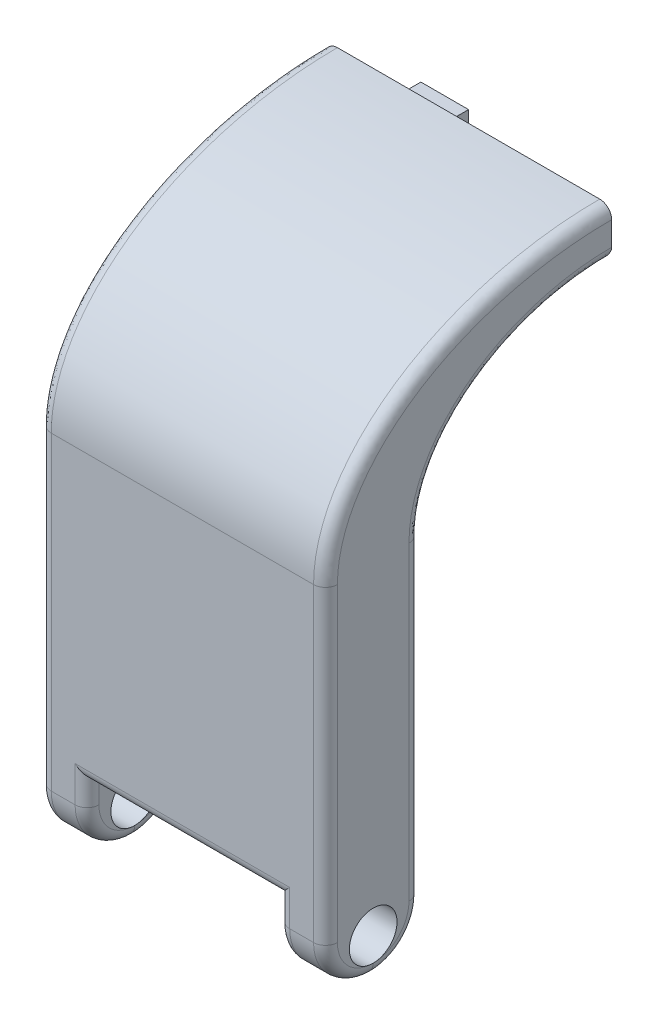
SolidWorks part; units mm, degrees
ref_plane "Front Plane" through (0, 0, 0) normal (0, 0, 1) x (1, 0, 0)
ref_plane "Top Plane" through (0, 0, 0) normal (0, 1, 0) x (1, 0, 0)
ref_plane "Right Plane" through (0, 0, 0) normal (1, 0, 0) x (0, 0, -1)
sketch "Sketch1" plane through (0, 0, 0) normal (0, 1, 0) x (1, 0, 0)
  line L1 (0, 0) -> (60, 0)
  line L2 (0, 0) -> (0, -20)
  line L3 (0, -20) -> (60, -20)
  line L4 (60, 0) -> (60, -20)
  dimension "D1" = 20
  dimension "D2" = 60
extrude "Boss-Extrude1" add sketch "Sketch1" against normal blind 30
sketch "Sketch2" plane through (0, -30, 0) normal (0, -1, 0) x (1, 0, 0)
  line L0 (60, 0) -> (0, 0) construction
  line L1 (10, 0) -> (50, 0)
  line L2 (10, 0) -> (10, 20)
  line L3 (10, 20) -> (50, 20)
  line L4 (50, 0) -> (50, 20)
  line L5 (0, 20) -> (60, 20) construction
  line L6 (0, 0) -> (0, 20) construction
  dimension "D1" = 40
  dimension "D2" = 10
extrude "Cut-Extrude1" cut sketch "Sketch2" against normal blind 15
sketch "Sketch3" plane through (10, 0, 0) normal (1, 0, 0) x (0, 0, -1)
  circle A0 centre (-10, -22.5) radius 5
  dimension "D1" = 10
extrude "Cut-Extrude2" cut sketch "Sketch3" against normal through all and the other way through all
sketch "Sketch5" plane through (0, 0, 0) normal (0, 1, 0) x (1, 0, 0)
  line L1 (0, 0) -> (60, 0)
  line L2 (0, 0) -> (0, -20)
  line L3 (0, -20) -> (60, -20)
  line L4 (60, 0) -> (60, -20)
extrude "Boss-Extrude2" add sketch "Sketch5" along normal blind 45
sketch "Sketch6" plane through (0, 0, 0) normal (1, 0, 0) x (0, 0, -1)
  line L0 (0, 45) -> (40, 45) construction
  line L1 (40, 45) -> (40, 75) construction
  line L2 (40, 85) -> (40, 75)
  line L3 (0, 45) -> (-20, 45)
  ellipse E0 centre (40, 45) end of major axis (0, 45) minor radius 30 (0, 45) -> (40, 75) cw
  ellipse E1 centre (40, 45) end of major axis (100, 45) minor radius 40 (-20, 45) -> (40, 85) cw
  dimension "D1" = 40
  dimension "D2" = 30
  dimension "D3" = 40
extrude "Boss-Extrude3" add sketch "Sketch6" along normal blind 60
sketch "Sketch8" plane through (0, 0, -40) normal (0, 0, -1) x (-1, 0, 0)
  line L0 (-60, 85) -> (0, 85) construction
  line L1 (-15, 82.5) -> (-25, 82.5)
  line L2 (-15, 82.5) -> (-15, 77.5)
  line L3 (-15, 77.5) -> (-25, 77.5)
  line L4 (-25, 82.5) -> (-25, 77.5)
  point P6 (-30, 85)
  dimension "D1" = 10
  dimension "D2" = 5
  dimension "D3" = 2.5
  dimension "D4" = 5
extrude "Boss-Extrude5" add sketch "Sketch8" along normal blind 5
fillet "Fillet1" radius 10 4 edges at (5, -30, 20) (5, -30, 0) (55, -30, 20) (55, -30, 0)
fillet "Fillet2" radius 2.5 26 edges at (0, 73.2843, 2.4264) (0, 12.5, 20) (0, -27.0711, 17.0711) (0, -27.0711, 2.9289) (0, 66.2132, -11.7157) (60, 73.2843, 2.4264) (60, 12.5, 20) (60, -27.0711, 17.0711) (60, -27.0711, 2.9289) (60, 66.2132, -11.7157) (10, -17.5, 20) (10, -27.0711, 17.0711) (10, -27.0711, 2.9289) (50, -17.5, 20) (50, -27.0711, 17.0711) (50, -27.0711, 2.9289) (15, 77.5, -42.5) (25, 77.5, -42.5) (20, 77.5, -45) (30, 75, -40) (30, -15, 20) (0, 12.5, 0) (60, 12.5, 0) (10, -17.5, 0) (50, -17.5, 0) (30, -15, 0)
